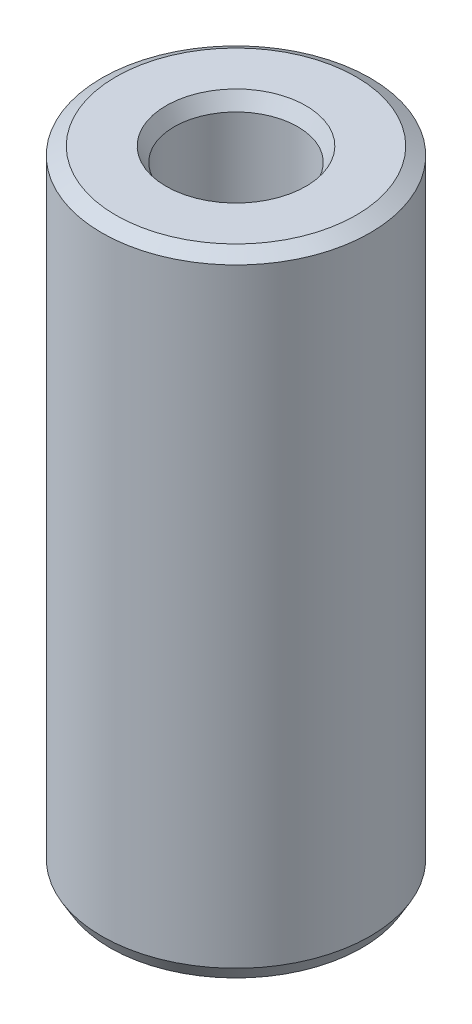
SolidWorks part; units mm, degrees
ref_plane "Front Plane" through (0, 0, 0) normal (0, 0, 1) x (1, 0, 0)
ref_plane "Top Plane" through (0, 0, 0) normal (0, 1, 0) x (1, 0, 0)
ref_plane "Right Plane" through (0, 0, 0) normal (1, 0, 0) x (0, 0, -1)
sketch "Sketch1" plane through (0, 0, 0) normal (0, 1, 0) x (1, 0, 0)
  circle A0 centre (0, 0) radius 40
  dimension "SLEEVE_OD" = 80
extrude "Boss-Extrude1" add sketch "Sketch1" along normal blind 188.2359
sketch "Sketch2" plane through (0, 0, 0) normal (0, 1, 0) x (1, 0, 0)
  circle A0 centre (0, 0) radius 18.4066
  dimension "BORE_D" = 36.8131
extrude "Cut-Extrude1" cut sketch "Sketch2" along normal through all
chamfer "Chamfer1" distance 2.4349 angle 60 4 edges at (0, 188.2359, 18.4066) (0, 0, 18.4066) (0, 0, 40) (0, 188.2359, 40) first distance on face at (0, 188.2359, 18.4066) first distance on face at (0, 0, 18.4066) first distance on face at (0, 188.2359, 40)
